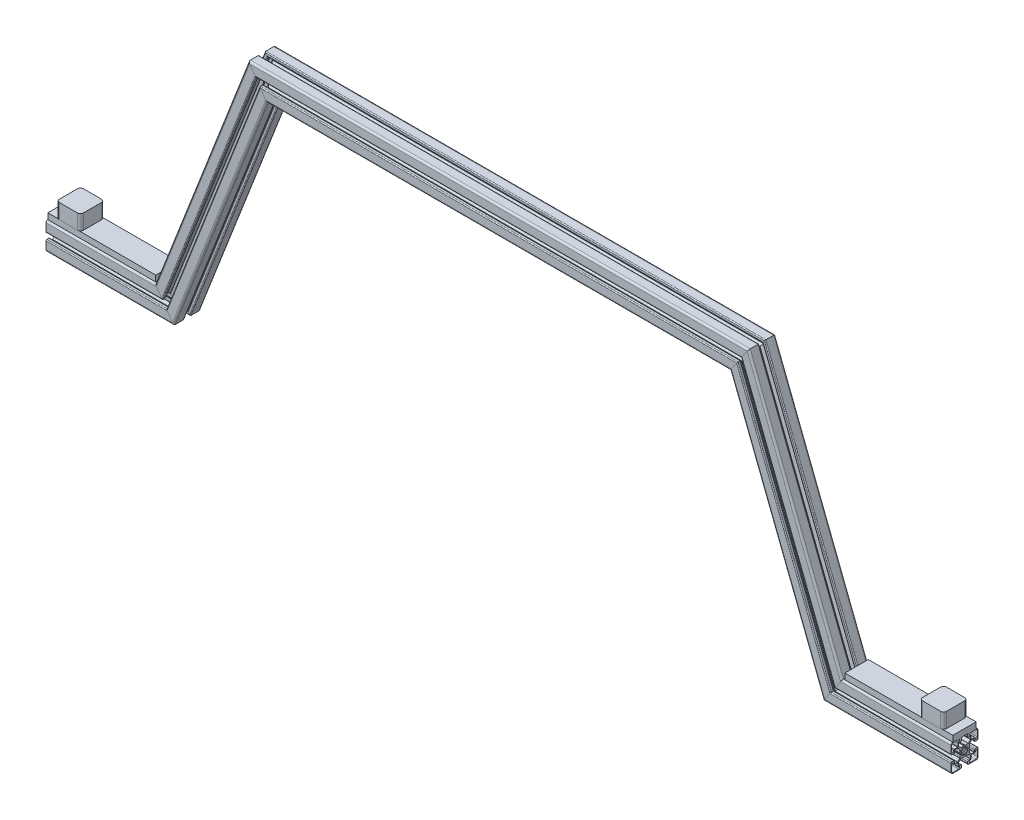
SolidWorks part; units mm, degrees
material "Commercially Pure CP-Ti UNS R50400 (SS)"
ref_plane "Front Plane" through (0, 0, 0) normal (0, 0, 1) x (1, 0, 0)
ref_plane "Top Plane" through (0, 0, 0) normal (0, 1, 0) x (1, 0, 0)
ref_plane "Right Plane" through (0, 0, 0) normal (1, 0, 0) x (0, 0, -1)
sketch "Sketch5" plane through (0, 0, 0) normal (1, 0, 0) x (0, 0, -1)
  line L0 (13.9698, 21.2743) -> (13.5298, 21.2743)
  line L1 (12.0298, 22.7743) -> (12.0298, 23.2743)
  line L2 (13.5298, 24.7743) -> (23.1398, 24.7743)
  line L3 (25.4198, 22.4943) -> (25.4198, 12.8843)
  line L4 (23.9198, 11.3843) -> (23.4198, 11.3843)
  line L5 (21.9198, 12.8843) -> (21.9198, 13.3243)
  line L6 (20.9198, 14.3243) -> (15.3498, 14.3243)
  line L7 (14.9698, 14.7043) -> (14.9698, 20.2743)
  line L8 (21.9589, -6.6897) -> (21.9589, -6.2497)
  line L9 (23.4589, -4.7497) -> (23.9589, -4.7497)
  line L10 (25.4589, -6.2497) -> (25.4589, -15.8597)
  line L11 (23.1789, -18.1397) -> (13.5689, -18.1397)
  line L12 (12.0689, -16.6397) -> (12.0689, -16.1397)
  line L13 (13.5689, -14.6397) -> (14.0089, -14.6397)
  line L14 (15.0089, -13.6397) -> (15.0089, -8.0697)
  line L15 (15.3889, -7.6897) -> (20.9589, -7.6897)
  line L16 (-6.0052, -14.6787) -> (-5.5652, -14.6787)
  line L17 (-4.0652, -16.1787) -> (-4.0652, -16.6787)
  line L18 (-5.5652, -18.1787) -> (-15.1752, -18.1787)
  line L19 (-17.4552, -15.8987) -> (-17.4552, -6.2887)
  line L20 (-15.9552, -4.7887) -> (-15.4552, -4.7887)
  line L21 (-13.9552, -6.2887) -> (-13.9552, -6.7287)
  line L22 (-12.9552, -7.7287) -> (-7.3852, -7.7287)
  line L23 (-7.0052, -8.1087) -> (-7.0052, -13.6787)
  line L24 (1.8289, -2.4886) -> (1.4132, -2.3164)
  line L25 (-1.632, 0.7289) -> (-1.8042, 1.1447)
  line L26 (-1.804, 5.4512) -> (-1.6318, 5.867)
  line L27 (1.4134, 8.9121) -> (1.8292, 9.0843)
  line L28 (6.1358, 9.0842) -> (6.5515, 8.912)
  line L29 (9.5966, 5.8667) -> (9.7688, 5.451)
  line L30 (9.7687, 1.1444) -> (9.5965, 0.7287)
  line L31 (6.5512, -2.3165) -> (6.1355, -2.4887)
  line L32 (-13.9942, 13.2853) -> (-13.9942, 12.8453)
  line L33 (-15.4942, 11.3453) -> (-15.9942, 11.3453)
  line L34 (-17.4942, 12.8453) -> (-17.4942, 22.4553)
  line L35 (-15.2142, 24.7353) -> (-5.6042, 24.7353)
  line L36 (-4.1042, 23.2353) -> (-4.1042, 22.7353)
  line L37 (-5.6042, 21.2353) -> (-6.0442, 21.2353)
  line L38 (-7.0442, 20.2353) -> (-7.0442, 14.6653)
  line L39 (-7.4242, 14.2853) -> (-12.9942, 14.2853)
  line L40 (4.9058, 11.2153) -> (4.0058, 10.7002)
  line L41 (4.0058, 10.7002) -> (3.1058, 11.2153)
  line L42 (3.1058, 11.2153) -> (-2.1975, 11.2153)
  line L43 (-2.4662, 11.3266) -> (-5.9329, 14.7933)
  line L44 (-6.0442, 15.062) -> (-6.0442, 19.3553)
  line L45 (-5.6642, 19.7353) -> (-2.5792, 19.7353)
  line L46 (-1.0592, 21.2553) -> (-1.0592, 24.2153)
  line L47 (-2.5792, 25.7353) -> (-15.4942, 25.7353)
  line L48 (-18.4942, 22.7353) -> (-18.4942, 9.8203)
  line L49 (-16.9742, 8.3003) -> (-14.0142, 8.3003)
  line L50 (-12.4942, 9.8203) -> (-12.4942, 12.9053)
  line L51 (-12.1142, 13.2853) -> (-7.8138, 13.2853)
  line L52 (-7.5451, 13.174) -> (-4.0855, 9.7144)
  line L53 (-3.9742, 9.4457) -> (-3.9742, 4.1353)
  line L54 (-3.9742, 4.1353) -> (-3.4546, 3.2353)
  line L55 (-3.4546, 3.2353) -> (-3.9742, 2.3353)
  line L56 (-3.9742, 2.3353) -> (-3.9742, -2.968)
  line L57 (-4.0855, -3.2367) -> (-7.5522, -6.7034)
  line L58 (-7.8209, -6.8147) -> (-12.1142, -6.8147)
  line L59 (-12.4942, -6.4347) -> (-12.4942, -3.3497)
  line L60 (-14.0142, -1.8297) -> (-16.9742, -1.8297)
  line L61 (-18.4942, -3.3497) -> (-18.4942, -16.2647)
  line L62 (-15.4942, -19.2647) -> (-2.5792, -19.2647)
  line L63 (-1.0592, -17.7447) -> (-1.0592, -14.7847)
  line L64 (-2.5792, -13.2647) -> (-5.6642, -13.2647)
  line L65 (-6.0442, -12.8847) -> (-6.0442, -8.5843)
  line L66 (-5.9329, -8.3156) -> (-2.4733, -4.856)
  line L67 (-2.2046, -4.7447) -> (3.1058, -4.7447)
  line L68 (3.1058, -4.7447) -> (4.0058, -4.2295)
  line L69 (4.0058, -4.2295) -> (4.9058, -4.7447)
  line L70 (4.9058, -4.7447) -> (10.2091, -4.7447)
  line L71 (10.4778, -4.856) -> (13.9445, -8.3227)
  line L72 (14.0558, -8.5914) -> (14.0558, -12.8847)
  line L73 (13.6758, -13.2647) -> (10.5908, -13.2647)
  line L74 (9.0708, -14.7847) -> (9.0708, -17.7447)
  line L75 (10.5908, -19.2647) -> (23.5058, -19.2647)
  line L76 (26.5058, -16.2647) -> (26.5058, -3.3497)
  line L77 (24.9858, -1.8297) -> (22.0258, -1.8297)
  line L78 (20.5058, -3.3497) -> (20.5058, -6.4347)
  line L79 (20.1258, -6.8147) -> (15.8254, -6.8147)
  line L80 (15.5567, -6.7034) -> (12.0971, -3.2438)
  line L81 (11.9858, -2.9751) -> (11.9858, 2.3353)
  line L82 (11.9858, 2.3353) -> (11.4662, 3.2353)
  line L83 (11.4662, 3.2353) -> (11.9858, 4.1353)
  line L84 (11.9858, 4.1353) -> (11.9858, 9.4386)
  line L85 (12.0971, 9.7073) -> (15.5638, 13.174)
  line L86 (15.8325, 13.2853) -> (20.1258, 13.2853)
  line L87 (20.5058, 12.9053) -> (20.5058, 9.8203)
  line L88 (22.0258, 8.3003) -> (24.9858, 8.3003)
  line L89 (26.5058, 9.8203) -> (26.5058, 22.7353)
  line L90 (23.5058, 25.7353) -> (10.5908, 25.7353)
  line L91 (9.0708, 24.2153) -> (9.0708, 21.2553)
  line L92 (10.5908, 19.7353) -> (13.6758, 19.7353)
  line L93 (14.0558, 19.3553) -> (14.0558, 15.0549)
  line L94 (13.9445, 14.7862) -> (10.4849, 11.3266)
  line L95 (10.2162, 11.2153) -> (4.9058, 11.2153)
  arc A0 (14.9698, 20.2743) -> (13.9698, 21.2743) centre (13.9698, 20.2743) ccw
  arc A1 (12.0298, 22.7743) -> (13.5298, 21.2743) centre (13.5298, 22.7743) ccw
  arc A2 (13.5298, 24.7743) -> (12.0298, 23.2743) centre (13.5298, 23.2743) ccw
  arc A3 (25.4198, 22.4943) -> (23.1398, 24.7743) centre (23.1398, 22.4943) ccw
  arc A4 (23.9198, 11.3843) -> (25.4198, 12.8843) centre (23.9198, 12.8843) ccw
  arc A5 (21.9198, 12.8843) -> (23.4198, 11.3843) centre (23.4198, 12.8843) ccw
  arc A6 (21.9198, 13.3243) -> (20.9198, 14.3243) centre (20.9198, 13.3243) ccw
  arc A7 (14.9698, 14.7043) -> (15.3498, 14.3243) centre (15.3498, 14.7043) ccw
  arc A8 (20.9589, -7.6897) -> (21.9589, -6.6897) centre (20.9589, -6.6897) ccw
  arc A9 (23.4589, -4.7497) -> (21.9589, -6.2497) centre (23.4589, -6.2497) ccw
  arc A10 (25.4589, -6.2497) -> (23.9589, -4.7497) centre (23.9589, -6.2497) ccw
  arc A11 (23.1789, -18.1397) -> (25.4589, -15.8597) centre (23.1789, -15.8597) ccw
  arc A12 (12.0689, -16.6397) -> (13.5689, -18.1397) centre (13.5689, -16.6397) ccw
  arc A13 (13.5689, -14.6397) -> (12.0689, -16.1397) centre (13.5689, -16.1397) ccw
  arc A14 (14.0089, -14.6397) -> (15.0089, -13.6397) centre (14.0089, -13.6397) ccw
  arc A15 (15.3889, -7.6897) -> (15.0089, -8.0697) centre (15.3889, -8.0697) ccw
  arc A16 (-7.0052, -13.6787) -> (-6.0052, -14.6787) centre (-6.0052, -13.6787) ccw
  arc A17 (-4.0652, -16.1787) -> (-5.5652, -14.6787) centre (-5.5652, -16.1787) ccw
  arc A18 (-5.5652, -18.1787) -> (-4.0652, -16.6787) centre (-5.5652, -16.6787) ccw
  arc A19 (-17.4552, -15.8987) -> (-15.1752, -18.1787) centre (-15.1752, -15.8987) ccw
  arc A20 (-15.9552, -4.7887) -> (-17.4552, -6.2887) centre (-15.9552, -6.2887) ccw
  arc A21 (-13.9552, -6.2887) -> (-15.4552, -4.7887) centre (-15.4552, -6.2887) ccw
  arc A22 (-13.9552, -6.7287) -> (-12.9552, -7.7287) centre (-12.9552, -6.7287) ccw
  arc A23 (-7.0052, -8.1087) -> (-7.3852, -7.7287) centre (-7.3852, -8.1087) ccw
  arc A24 (1.0363, -0.7421) -> (1.4132, -2.3164) centre (1.7959, -1.3925) ccw
  arc A25 (-0.0577, 0.352) -> (1.0363, -0.7421) centre (3.9823, 3.2978) ccw
  arc A26 (-1.632, 0.7289) -> (-0.0577, 0.352) centre (-0.7081, 1.1116) ccw
  arc A27 (-0.9575, 2.5244) -> (-1.8042, 1.1447) centre (-0.8803, 1.5274) ccw
  arc A28 (-0.9574, 4.0715) -> (-0.9575, 2.5244) centre (3.9823, 3.2978) ccw
  arc A29 (-1.804, 5.4512) -> (-0.9574, 4.0715) centre (-0.8802, 5.0686) ccw
  arc A30 (-0.0575, 6.2439) -> (-1.6318, 5.867) centre (-0.708, 5.4843) ccw
  arc A31 (1.0365, 7.3379) -> (-0.0575, 6.2439) centre (3.9823, 3.2978) ccw
  arc A32 (1.4134, 8.9121) -> (1.0365, 7.3379) centre (1.7961, 7.9882) ccw
  arc A33 (3.2089, 8.2376) -> (1.8292, 9.0843) centre (2.2119, 8.1604) ccw
  arc A34 (4.7561, 8.2376) -> (3.2089, 8.2376) centre (3.9823, 3.2978) ccw
  arc A35 (6.1358, 9.0842) -> (4.7561, 8.2376) centre (5.7531, 8.1603) ccw
  arc A36 (6.9284, 7.3377) -> (6.5515, 8.912) centre (6.1688, 7.9881) ccw
  arc A37 (8.0224, 6.2437) -> (6.9284, 7.3377) centre (3.9823, 3.2978) ccw
  arc A38 (9.5966, 5.8667) -> (8.0224, 6.2437) centre (8.6727, 5.484) ccw
  arc A39 (8.9222, 4.0713) -> (9.7688, 5.451) centre (8.845, 5.0683) ccw
  arc A40 (8.9221, 2.5241) -> (8.9222, 4.0713) centre (3.9823, 3.2978) ccw
  arc A41 (9.7687, 1.1444) -> (8.9221, 2.5241) centre (8.8448, 1.5271) ccw
  arc A42 (8.0222, 0.3518) -> (9.5965, 0.7287) centre (8.6726, 1.1113) ccw
  arc A43 (6.9282, -0.7422) -> (8.0222, 0.3518) centre (3.9823, 3.2978) ccw
  arc A44 (6.5512, -2.3165) -> (6.9282, -0.7422) centre (6.1685, -1.3926) ccw
  arc A45 (4.7558, -1.642) -> (6.1355, -2.4887) centre (5.7528, -1.5648) ccw
  arc A46 (3.2086, -1.642) -> (4.7558, -1.642) centre (3.9823, 3.2978) ccw
  arc A47 (1.8289, -2.4886) -> (3.2086, -1.642) centre (2.2116, -1.5647) ccw
  arc A48 (-12.9942, 14.2853) -> (-13.9942, 13.2853) centre (-12.9942, 13.2853) ccw
  arc A49 (-15.4942, 11.3453) -> (-13.9942, 12.8453) centre (-15.4942, 12.8453) ccw
  arc A50 (-17.4942, 12.8453) -> (-15.9942, 11.3453) centre (-15.9942, 12.8453) ccw
  arc A51 (-15.2142, 24.7353) -> (-17.4942, 22.4553) centre (-15.2142, 22.4553) ccw
  arc A52 (-4.1042, 23.2353) -> (-5.6042, 24.7353) centre (-5.6042, 23.2353) ccw
  arc A53 (-5.6042, 21.2353) -> (-4.1042, 22.7353) centre (-5.6042, 22.7353) ccw
  arc A54 (-6.0442, 21.2353) -> (-7.0442, 20.2353) centre (-6.0442, 20.2353) ccw
  arc A55 (-7.4242, 14.2853) -> (-7.0442, 14.6653) centre (-7.4242, 14.6653) ccw
  arc A56 (-2.4662, 11.3266) -> (-2.1975, 11.2153) centre (-2.1975, 11.5953) ccw
  arc A57 (-6.0442, 15.062) -> (-5.9329, 14.7933) centre (-5.6642, 15.062) ccw
  arc A58 (-5.6642, 19.7353) -> (-6.0442, 19.3553) centre (-5.6642, 19.3553) ccw
  arc A59 (-2.5792, 19.7353) -> (-1.0592, 21.2553) centre (-2.5792, 21.2553) ccw
  arc A60 (-1.0592, 24.2153) -> (-2.5792, 25.7353) centre (-2.5792, 24.2153) ccw
  arc A61 (-15.4942, 25.7353) -> (-18.4942, 22.7353) centre (-15.4942, 22.7353) ccw
  arc A62 (-18.4942, 9.8203) -> (-16.9742, 8.3003) centre (-16.9742, 9.8203) ccw
  arc A63 (-14.0142, 8.3003) -> (-12.4942, 9.8203) centre (-14.0142, 9.8203) ccw
  arc A64 (-12.1142, 13.2853) -> (-12.4942, 12.9053) centre (-12.1142, 12.9053) ccw
  arc A65 (-7.5451, 13.174) -> (-7.8138, 13.2853) centre (-7.8138, 12.9053) ccw
  arc A66 (-3.9742, 9.4457) -> (-4.0855, 9.7144) centre (-4.3542, 9.4457) ccw
  arc A67 (-4.0855, -3.2367) -> (-3.9742, -2.968) centre (-4.3542, -2.968) ccw
  arc A68 (-7.8209, -6.8147) -> (-7.5522, -6.7034) centre (-7.8209, -6.4347) ccw
  arc A69 (-12.4942, -6.4347) -> (-12.1142, -6.8147) centre (-12.1142, -6.4347) ccw
  arc A70 (-12.4942, -3.3497) -> (-14.0142, -1.8297) centre (-14.0142, -3.3497) ccw
  arc A71 (-16.9742, -1.8297) -> (-18.4942, -3.3497) centre (-16.9742, -3.3497) ccw
  arc A72 (-18.4942, -16.2647) -> (-15.4942, -19.2647) centre (-15.4942, -16.2647) ccw
  arc A73 (-2.5792, -19.2647) -> (-1.0592, -17.7447) centre (-2.5792, -17.7447) ccw
  arc A74 (-1.0592, -14.7847) -> (-2.5792, -13.2647) centre (-2.5792, -14.7847) ccw
  arc A75 (-6.0442, -12.8847) -> (-5.6642, -13.2647) centre (-5.6642, -12.8847) ccw
  arc A76 (-5.9329, -8.3156) -> (-6.0442, -8.5843) centre (-5.6642, -8.5843) ccw
  arc A77 (-2.2046, -4.7447) -> (-2.4733, -4.856) centre (-2.2046, -5.1247) ccw
  arc A78 (10.4778, -4.856) -> (10.2091, -4.7447) centre (10.2091, -5.1247) ccw
  arc A79 (14.0558, -8.5914) -> (13.9445, -8.3227) centre (13.6758, -8.5914) ccw
  arc A80 (13.6758, -13.2647) -> (14.0558, -12.8847) centre (13.6758, -12.8847) ccw
  arc A81 (10.5908, -13.2647) -> (9.0708, -14.7847) centre (10.5908, -14.7847) ccw
  arc A82 (9.0708, -17.7447) -> (10.5908, -19.2647) centre (10.5908, -17.7447) ccw
  arc A83 (23.5058, -19.2647) -> (26.5058, -16.2647) centre (23.5058, -16.2647) ccw
  arc A84 (26.5058, -3.3497) -> (24.9858, -1.8297) centre (24.9858, -3.3497) ccw
  arc A85 (22.0258, -1.8297) -> (20.5058, -3.3497) centre (22.0258, -3.3497) ccw
  arc A86 (20.1258, -6.8147) -> (20.5058, -6.4347) centre (20.1258, -6.4347) ccw
  arc A87 (15.5567, -6.7034) -> (15.8254, -6.8147) centre (15.8254, -6.4347) ccw
  arc A88 (11.9858, -2.9751) -> (12.0971, -3.2438) centre (12.3658, -2.9751) ccw
  arc A89 (12.0971, 9.7073) -> (11.9858, 9.4386) centre (12.3658, 9.4386) ccw
  arc A90 (15.8325, 13.2853) -> (15.5638, 13.174) centre (15.8325, 12.9053) ccw
  arc A91 (20.5058, 12.9053) -> (20.1258, 13.2853) centre (20.1258, 12.9053) ccw
  arc A92 (20.5058, 9.8203) -> (22.0258, 8.3003) centre (22.0258, 9.8203) ccw
  arc A93 (24.9858, 8.3003) -> (26.5058, 9.8203) centre (24.9858, 9.8203) ccw
  arc A94 (26.5058, 22.7353) -> (23.5058, 25.7353) centre (23.5058, 22.7353) ccw
  arc A95 (10.5908, 25.7353) -> (9.0708, 24.2153) centre (10.5908, 24.2153) ccw
  arc A96 (9.0708, 21.2553) -> (10.5908, 19.7353) centre (10.5908, 21.2553) ccw
  arc A97 (14.0558, 19.3553) -> (13.6758, 19.7353) centre (13.6758, 19.3553) ccw
  arc A98 (13.9445, 14.7862) -> (14.0558, 15.0549) centre (13.6758, 15.0549) ccw
  arc A99 (10.2162, 11.2153) -> (10.4849, 11.3266) centre (10.2162, 11.5953) ccw
sketch "Sketch1" plane through (0, 0, 0) normal (0, 0, 1) x (1, 0, 0)
  line L0 (0, 0) -> (200, 0)
  line L1 (200, 0) -> (355.8974, 400)
  line L2 (355.8974, 400) -> (755.8974, 400)
  dimension "D1" = 400
  dimension "D2" = 200
  dimension "D3" = 400
sketch "Sketch2" [suppressed] plane through (0, 0, 0) normal (1, 0, 0) x (0, 0, -1)
  line L0 (-33.5, -41) -> (-31.5, -41)
  line L1 (-31.5, -43) -> (-42, -43)
  line L2 (-43, -42) -> (-43, -31.5)
  line L3 (-41, -31.5) -> (-41, -33.5)
  line L4 (-40, -34.5) -> (-34.88, -34.5)
  line L5 (-34.5, -34.88) -> (-34.5, -40)
  line L6 (-16.657, -26.2238) -> (-18.284, -25.188)
  line L7 (-19.8123, -26.7162) -> (-18.7764, -28.3429)
  line L8 (-21.0015, -29.2647) -> (-21.4195, -27.3819)
  line L9 (-23.5808, -27.3818) -> (-23.9986, -29.2645)
  line L10 (-26.2238, -28.343) -> (-25.188, -26.716)
  line L11 (-26.7162, -25.1877) -> (-28.3429, -26.2236)
  line L12 (-29.2647, -23.9985) -> (-27.3819, -23.5805)
  line L13 (-27.3818, -21.4192) -> (-29.2645, -21.0014)
  line L14 (-28.343, -18.7762) -> (-26.716, -19.812)
  line L15 (-25.1877, -18.2838) -> (-26.2236, -16.6571)
  line L16 (-23.9985, -15.7353) -> (-23.5805, -17.6181)
  line L17 (-21.4192, -17.6182) -> (-21.0014, -15.7355)
  line L18 (-18.7762, -16.657) -> (-19.812, -18.284)
  line L19 (-18.2838, -19.8123) -> (-16.6571, -18.7764)
  line L20 (-15.7353, -21.0015) -> (-17.6181, -21.4195)
  line L21 (-17.6182, -23.5808) -> (-15.7355, -23.9986)
  line L22 (41, -33.5) -> (41, -31.5)
  line L23 (43, -31.5) -> (43, -42)
  line L24 (42, -43) -> (31.5, -43)
  line L25 (31.5, -41) -> (33.5, -41)
  line L26 (34.5, -40) -> (34.5, -34.88)
  line L27 (34.88, -34.5) -> (40, -34.5)
  line L28 (26.7162, -19.8123) -> (28.3429, -18.7764)
  line L29 (29.2647, -21.0015) -> (27.3819, -21.4195)
  line L30 (27.3818, -23.5808) -> (29.2645, -23.9986)
  line L31 (28.343, -26.2238) -> (26.716, -25.188)
  line L32 (25.1877, -26.7162) -> (26.2236, -28.3429)
  line L33 (23.9985, -29.2647) -> (23.5805, -27.3819)
  line L34 (21.4192, -27.3818) -> (21.0014, -29.2645)
  line L35 (18.7762, -28.343) -> (19.812, -26.716)
  line L36 (18.2838, -25.1877) -> (16.6571, -26.2236)
  line L37 (15.7353, -23.9985) -> (17.6181, -23.5805)
  line L38 (17.6182, -21.4192) -> (15.7355, -21.0014)
  line L39 (16.657, -18.7762) -> (18.284, -19.812)
  line L40 (19.8123, -18.2838) -> (18.7764, -16.6571)
  line L41 (21.0015, -15.7353) -> (21.4195, -17.6181)
  line L42 (23.5808, -17.6182) -> (23.9986, -15.7355)
  line L43 (26.2238, -16.657) -> (25.188, -18.284)
  line L44 (34.5, 34.88) -> (34.5, 40)
  line L45 (33.5, 41) -> (31.5, 41)
  line L46 (31.5, 43) -> (42, 43)
  line L47 (43, 42) -> (43, 31.5)
  line L48 (41, 31.5) -> (41, 33.5)
  line L49 (40, 34.5) -> (34.88, 34.5)
  line L50 (26.7162, 25.1877) -> (28.3429, 26.2236)
  line L51 (29.2647, 23.9985) -> (27.3819, 23.5805)
  line L52 (27.3818, 21.4192) -> (29.2645, 21.0014)
  line L53 (28.343, 18.7762) -> (26.716, 19.812)
  line L54 (25.1877, 18.2838) -> (26.2236, 16.6571)
  line L55 (23.9985, 15.7353) -> (23.5805, 17.6181)
  line L56 (21.4192, 17.6182) -> (21.0014, 15.7355)
  line L57 (18.7762, 16.657) -> (19.812, 18.284)
  line L58 (18.2838, 19.8123) -> (16.6571, 18.7764)
  line L59 (15.7353, 21.0015) -> (17.6181, 21.4195)
  line L60 (17.6182, 23.5808) -> (15.7355, 23.9986)
  line L61 (16.657, 26.2238) -> (18.284, 25.188)
  line L62 (19.8123, 26.7162) -> (18.7764, 28.3429)
  line L63 (21.0015, 29.2647) -> (21.4195, 27.3819)
  line L64 (23.5808, 27.3818) -> (23.9986, 29.2645)
  line L65 (26.2238, 28.343) -> (25.188, 26.716)
  line L66 (-41, 33.5) -> (-41, 31.5)
  line L67 (-43, 31.5) -> (-43, 42)
  line L68 (-42, 43) -> (-31.5, 43)
  line L69 (-31.5, 41) -> (-33.5, 41)
  line L70 (-34.5, 40) -> (-34.5, 34.88)
  line L71 (-34.88, 34.5) -> (-40, 34.5)
  line L72 (-16.657, 18.7762) -> (-18.284, 19.812)
  line L73 (-19.8123, 18.2838) -> (-18.7764, 16.6571)
  line L74 (-21.0015, 15.7353) -> (-21.4195, 17.6181)
  line L75 (-23.5808, 17.6182) -> (-23.9986, 15.7355)
  line L76 (-26.2238, 16.657) -> (-25.188, 18.284)
  line L77 (-26.7162, 19.8123) -> (-28.3429, 18.7764)
  line L78 (-29.2647, 21.0015) -> (-27.3819, 21.4195)
  line L79 (-27.3818, 23.5808) -> (-29.2645, 23.9986)
  line L80 (-28.343, 26.2238) -> (-26.716, 25.188)
  line L81 (-25.1877, 26.7162) -> (-26.2236, 28.3429)
  line L82 (-23.9985, 29.2647) -> (-23.5805, 27.3819)
  line L83 (-21.4192, 27.3818) -> (-21.0014, 29.2645)
  line L84 (-18.7762, 28.343) -> (-19.812, 26.716)
  line L85 (-18.2838, 25.1877) -> (-16.6571, 26.2236)
  line L86 (-15.7353, 23.9985) -> (-17.6181, 23.5805)
  line L87 (-17.6182, 21.4192) -> (-15.7355, 21.0014)
  line L88 (39, -10.16) -> (33.3774, -10.16)
  line L89 (31.9632, -10.7458) -> (29.8203, -12.8887)
  line L90 (29.5516, -13) -> (23.4, -13)
  line L91 (23.4, -13) -> (22.5, -13.5151)
  line L92 (22.5, -13.5151) -> (21.6, -13)
  line L93 (21.6, -13) -> (15, -13)
  line L94 (13, -15) -> (13, -21.6)
  line L95 (13, -21.6) -> (13.5196, -22.5)
  line L96 (13.5196, -22.5) -> (13, -23.4)
  line L97 (13, -23.4) -> (13, -29.5516)
  line L98 (12.8887, -29.8203) -> (11.3787, -31.3303)
  line L99 (10.5, -33.4516) -> (10.5, -40)
  line L100 (11.5, -41) -> (13.5, -41)
  line L101 (13.5, -43) -> (-13.5, -43)
  line L102 (-13.5, -41) -> (-11.5, -41)
  line L103 (-10.5, -40) -> (-10.5, -33.4516)
  line L104 (-11.3787, -31.3303) -> (-12.8887, -29.8203)
  line L105 (-13, -29.5516) -> (-13, -23.4)
  line L106 (-13, -23.4) -> (-13.5196, -22.5)
  line L107 (-13.5196, -22.5) -> (-13, -21.6)
  line L108 (-13, -21.6) -> (-13, -15)
  line L109 (-15, -13) -> (-21.6, -13)
  line L110 (-21.6, -13) -> (-22.5, -13.5151)
  line L111 (-22.5, -13.5151) -> (-23.4, -13)
  line L112 (-23.4, -13) -> (-29.5516, -13)
  line L113 (-29.8203, -12.8887) -> (-31.9632, -10.7458)
  line L114 (-33.3774, -10.16) -> (-39, -10.16)
  line L115 (-41, -12.16) -> (-41, -13.5)
  line L116 (-43, -13.5) -> (-43, 13.5)
  line L117 (-41, 13.5) -> (-41, 12.16)
  line L118 (-39, 10.16) -> (-33.3774, 10.16)
  line L119 (-31.9632, 10.7458) -> (-29.8203, 12.8887)
  line L120 (-29.5516, 13) -> (-23.4, 13)
  line L121 (-23.4, 13) -> (-22.5, 13.5151)
  line L122 (-22.5, 13.5151) -> (-21.6, 13)
  line L123 (-21.6, 13) -> (-15, 13)
  line L124 (-13, 15) -> (-13, 21.6)
  line L125 (-13, 21.6) -> (-13.5196, 22.5)
  line L126 (-13.5196, 22.5) -> (-13, 23.4)
  line L127 (-13, 23.4) -> (-13, 29.5516)
  line L128 (-12.8887, 29.8203) -> (-11.3787, 31.3303)
  line L129 (-10.5, 33.4516) -> (-10.5, 40)
  line L130 (-11.5, 41) -> (-13.5, 41)
  line L131 (-13.5, 43) -> (13.5, 43)
  line L132 (13.5, 41) -> (11.5, 41)
  line L133 (10.5, 40) -> (10.5, 33.4516)
  line L134 (11.3787, 31.3303) -> (12.8887, 29.8203)
  line L135 (13, 29.5516) -> (13, 23.4)
  line L136 (13, 23.4) -> (13.5196, 22.5)
  line L137 (13.5196, 22.5) -> (13, 21.6)
  line L138 (13, 21.6) -> (13, 15)
  line L139 (15, 13) -> (21.6, 13)
  line L140 (21.6, 13) -> (22.5, 13.5151)
  line L141 (22.5, 13.5151) -> (23.4, 13)
  line L142 (23.4, 13) -> (29.5516, 13)
  line L143 (29.8203, 12.8887) -> (31.9581, 10.7509)
  line L144 (33.3723, 10.1651) -> (39, 10.1651)
  line L145 (41, 12.1651) -> (41, 13.5)
  line L146 (43, 13.5) -> (43, -13.5)
  line L147 (41, -13.5) -> (41, -12.16)
  line L148 (45, -15.915) -> (45, 15.915)
  line L149 (43.48, 17.435) -> (40.52, 17.435)
  line L150 (39, 15.915) -> (39, 13.45)
  line L151 (38, 12.45) -> (34.9984, 12.45)
  line L152 (34.7297, 12.5613) -> (32.1113, 15.1797)
  line L153 (32, 15.4484) -> (32, 21.6)
  line L154 (32, 21.6) -> (31.4804, 22.5)
  line L155 (31.4804, 22.5) -> (32, 23.4)
  line L156 (32, 23.4) -> (32, 29.5516)
  line L157 (32.1113, 29.8203) -> (34.7297, 32.4387)
  line L158 (34.9984, 32.55) -> (38, 32.55)
  line L159 (39, 31.55) -> (39, 29.085)
  line L160 (40.52, 27.565) -> (43.48, 27.565)
  line L161 (45, 29.085) -> (45, 42)
  line L162 (42, 45) -> (29.085, 45)
  line L163 (27.565, 43.48) -> (27.565, 40.52)
  line L164 (29.085, 39) -> (31.55, 39)
  line L165 (32.55, 38) -> (32.55, 34.9984)
  line L166 (32.4387, 34.7297) -> (29.8203, 32.1113)
  line L167 (29.5516, 32) -> (23.4, 32)
  line L168 (23.4, 32) -> (22.5, 31.4849)
  line L169 (22.5, 31.4849) -> (21.6, 32)
  line L170 (21.6, 32) -> (15.4484, 32)
  line L171 (15.1797, 32.1113) -> (12.5613, 34.7297)
  line L172 (12.45, 34.9984) -> (12.45, 38)
  line L173 (13.45, 39) -> (15.915, 39)
  line L174 (17.435, 40.52) -> (17.435, 43.48)
  line L175 (15.915, 45) -> (-15.915, 45)
  line L176 (-17.435, 43.48) -> (-17.435, 40.52)
  line L177 (-15.915, 39) -> (-13.45, 39)
  line L178 (-12.45, 38) -> (-12.45, 34.9984)
  line L179 (-12.5613, 34.7297) -> (-15.1797, 32.1113)
  line L180 (-15.4484, 32) -> (-21.6, 32)
  line L181 (-21.6, 32) -> (-22.5, 31.4849)
  line L182 (-22.5, 31.4849) -> (-23.4, 32)
  line L183 (-23.4, 32) -> (-29.5516, 32)
  line L184 (-29.8203, 32.1113) -> (-32.4387, 34.7297)
  line L185 (-32.55, 34.9984) -> (-32.55, 38)
  line L186 (-31.55, 39) -> (-29.085, 39)
  line L187 (-27.565, 40.52) -> (-27.565, 43.48)
  line L188 (-29.085, 45) -> (-42, 45)
  line L189 (-45, 42) -> (-45, 29.085)
  line L190 (-43.48, 27.565) -> (-40.52, 27.565)
  line L191 (-39, 29.085) -> (-39, 31.55)
  line L192 (-38, 32.55) -> (-34.9984, 32.55)
  line L193 (-34.7297, 32.4387) -> (-32.1113, 29.8203)
  line L194 (-32, 29.5516) -> (-32, 23.4)
  line L195 (-32, 23.4) -> (-31.4804, 22.5)
  line L196 (-31.4804, 22.5) -> (-32, 21.6)
  line L197 (-32, 21.6) -> (-32, 15.4484)
  line L198 (-32.1113, 15.1797) -> (-34.7297, 12.5613)
  line L199 (-34.9984, 12.45) -> (-38, 12.45)
  line L200 (-39, 13.45) -> (-39, 15.915)
  line L201 (-40.52, 17.435) -> (-43.48, 17.435)
  line L202 (-45, 15.915) -> (-45, -15.915)
  line L203 (-43.48, -17.435) -> (-40.52, -17.435)
  line L204 (-39, -15.915) -> (-39, -13.45)
  line L205 (-38, -12.45) -> (-34.9984, -12.45)
  line L206 (-34.7297, -12.5613) -> (-32.1113, -15.1797)
  line L207 (-32, -15.4484) -> (-32, -21.6)
  line L208 (-32, -21.6) -> (-31.4804, -22.5)
  line L209 (-31.4804, -22.5) -> (-32, -23.4)
  line L210 (-32, -23.4) -> (-32, -29.5516)
  line L211 (-32.1113, -29.8203) -> (-34.7297, -32.4387)
  line L212 (-34.9984, -32.55) -> (-38, -32.55)
  line L213 (-39, -31.55) -> (-39, -29.085)
  line L214 (-40.52, -27.565) -> (-43.48, -27.565)
  line L215 (-45, -29.085) -> (-45, -42)
  line L216 (-42, -45) -> (-29.085, -45)
  line L217 (-27.565, -43.48) -> (-27.565, -40.52)
  line L218 (-29.085, -39) -> (-31.55, -39)
  line L219 (-32.55, -38) -> (-32.55, -34.9984)
  line L220 (-32.4387, -34.7297) -> (-29.8203, -32.1113)
  line L221 (-29.5516, -32) -> (-23.4, -32)
  line L222 (-23.4, -32) -> (-22.5, -31.4849)
  line L223 (-22.5, -31.4849) -> (-21.6, -32)
  line L224 (-21.6, -32) -> (-15.4484, -32)
  line L225 (-15.1797, -32.1113) -> (-12.5613, -34.7297)
  line L226 (-12.45, -34.9984) -> (-12.45, -38)
  line L227 (-13.45, -39) -> (-15.915, -39)
  line L228 (-17.435, -40.52) -> (-17.435, -43.48)
  line L229 (-15.915, -45) -> (15.915, -45)
  line L230 (17.435, -43.48) -> (17.435, -40.52)
  line L231 (15.915, -39) -> (13.45, -39)
  line L232 (12.45, -38) -> (12.45, -34.9984)
  line L233 (12.5613, -34.7297) -> (15.1797, -32.1113)
  line L234 (15.4484, -32) -> (21.6, -32)
  line L235 (21.6, -32) -> (22.5, -31.4849)
  line L236 (22.5, -31.4849) -> (23.4, -32)
  line L237 (23.4, -32) -> (29.5516, -32)
  line L238 (29.8203, -32.1113) -> (32.4387, -34.7297)
  line L239 (32.55, -34.9984) -> (32.55, -38)
  line L240 (31.55, -39) -> (29.085, -39)
  line L241 (27.565, -40.52) -> (27.565, -43.48)
  line L242 (29.085, -45) -> (42, -45)
  line L243 (45, -42) -> (45, -29.085)
  line L244 (43.48, -27.565) -> (40.52, -27.565)
  line L245 (39, -29.085) -> (39, -31.55)
  line L246 (38, -32.55) -> (34.9984, -32.55)
  line L247 (34.7297, -32.4387) -> (32.1113, -29.8203)
  line L248 (32, -29.5516) -> (32, -23.4)
  line L249 (32, -23.4) -> (31.4804, -22.5)
  line L250 (31.4804, -22.5) -> (32, -21.6)
  line L251 (32, -21.6) -> (32, -15.4484)
  line L252 (32.1113, -15.1797) -> (34.7297, -12.5613)
  line L253 (34.9984, -12.45) -> (38, -12.45)
  line L254 (39, -13.45) -> (39, -15.915)
  line L255 (40.52, -17.435) -> (43.48, -17.435)
  arc A0 (-34.5, -40) -> (-33.5, -41) centre (-33.5, -40) ccw
  arc A1 (-31.5, -43) -> (-31.5, -41) centre (-31.5, -42) ccw
  arc A2 (-43, -42) -> (-42, -43) centre (-42, -42) ccw
  arc A3 (-41, -31.5) -> (-43, -31.5) centre (-42, -31.5) ccw
  arc A4 (-41, -33.5) -> (-40, -34.5) centre (-40, -33.5) ccw
  arc A5 (-34.5, -34.88) -> (-34.88, -34.5) centre (-34.88, -34.88) ccw
  arc A6 (-15.2086, -25.7917) -> (-15.0167, -25.3284) centre (-22.5, -22.5) ccw
  arc A7 (-16.657, -26.2238) -> (-15.2086, -25.7917) centre (-16.12, -25.3802) ccw
  arc A8 (-19.8123, -26.7162) -> (-18.284, -25.188) centre (-22.5, -22.5) ccw
  arc A9 (-19.2085, -29.7915) -> (-18.7764, -28.3429) centre (-19.6199, -28.8801) ccw
  arc A10 (-19.6717, -29.9834) -> (-19.2085, -29.7915) centre (-22.5, -22.5) ccw
  arc A11 (-21.0015, -29.2647) -> (-19.6717, -29.9834) centre (-20.0253, -29.048) ccw
  arc A12 (-23.5808, -27.3818) -> (-21.4195, -27.3819) centre (-22.5, -22.5) ccw
  arc A13 (-25.3284, -29.9833) -> (-23.9986, -29.2645) centre (-24.9749, -29.0479) ccw
  arc A14 (-25.7917, -29.7914) -> (-25.3284, -29.9833) centre (-22.5, -22.5) ccw
  arc A15 (-26.2238, -28.343) -> (-25.7917, -29.7914) centre (-25.3802, -28.88) ccw
  arc A16 (-26.7162, -25.1877) -> (-25.188, -26.716) centre (-22.5, -22.5) ccw
  arc A17 (-29.7915, -25.7915) -> (-28.3429, -26.2236) centre (-28.8801, -25.3801) ccw
  arc A18 (-29.9834, -25.3283) -> (-29.7915, -25.7915) centre (-22.5, -22.5) ccw
  arc A19 (-29.2647, -23.9985) -> (-29.9834, -25.3283) centre (-29.048, -24.9747) ccw
  arc A20 (-27.3818, -21.4192) -> (-27.3819, -23.5805) centre (-22.5, -22.5) ccw
  arc A21 (-29.9833, -19.6716) -> (-29.2645, -21.0014) centre (-29.0479, -20.0251) ccw
  arc A22 (-29.7914, -19.2083) -> (-29.9833, -19.6716) centre (-22.5, -22.5) ccw
  arc A23 (-28.343, -18.7762) -> (-29.7914, -19.2083) centre (-28.88, -19.6198) ccw
  arc A24 (-25.1877, -18.2838) -> (-26.716, -19.812) centre (-22.5, -22.5) ccw
  arc A25 (-25.7915, -15.2085) -> (-26.2236, -16.6571) centre (-25.3801, -16.1199) ccw
  arc A26 (-25.3283, -15.0166) -> (-25.7915, -15.2085) centre (-22.5, -22.5) ccw
  arc A27 (-23.9985, -15.7353) -> (-25.3283, -15.0166) centre (-24.9747, -15.952) ccw
  arc A28 (-21.4192, -17.6182) -> (-23.5805, -17.6181) centre (-22.5, -22.5) ccw
  arc A29 (-19.6716, -15.0167) -> (-21.0014, -15.7355) centre (-20.0251, -15.9521) ccw
  arc A30 (-19.2083, -15.2086) -> (-19.6716, -15.0167) centre (-22.5, -22.5) ccw
  arc A31 (-18.7762, -16.657) -> (-19.2083, -15.2086) centre (-19.6198, -16.12) ccw
  arc A32 (-18.2838, -19.8123) -> (-19.812, -18.284) centre (-22.5, -22.5) ccw
  arc A33 (-15.2085, -19.2085) -> (-16.6571, -18.7764) centre (-16.1199, -19.6199) ccw
  arc A34 (-15.0166, -19.6717) -> (-15.2085, -19.2085) centre (-22.5, -22.5) ccw
  arc A35 (-15.7353, -21.0015) -> (-15.0166, -19.6717) centre (-15.952, -20.0253) ccw
  arc A36 (-17.6182, -23.5808) -> (-17.6181, -21.4195) centre (-22.5, -22.5) ccw
  arc A37 (-15.0167, -25.3284) -> (-15.7355, -23.9986) centre (-15.9521, -24.9749) ccw
  arc A38 (40, -34.5) -> (41, -33.5) centre (40, -33.5) ccw
  arc A39 (43, -31.5) -> (41, -31.5) centre (42, -31.5) ccw
  arc A40 (42, -43) -> (43, -42) centre (42, -42) ccw
  arc A41 (31.5, -41) -> (31.5, -43) centre (31.5, -42) ccw
  arc A42 (33.5, -41) -> (34.5, -40) centre (33.5, -40) ccw
  arc A43 (34.88, -34.5) -> (34.5, -34.88) centre (34.88, -34.88) ccw
  arc A44 (26.7162, -19.8123) -> (25.188, -18.284) centre (22.5, -22.5) ccw
  arc A45 (29.7915, -19.2085) -> (28.3429, -18.7764) centre (28.8801, -19.6199) ccw
  arc A46 (29.9834, -19.6717) -> (29.7915, -19.2085) centre (22.5, -22.5) ccw
  arc A47 (29.2647, -21.0015) -> (29.9834, -19.6717) centre (29.048, -20.0253) ccw
  arc A48 (27.3818, -23.5808) -> (27.3819, -21.4195) centre (22.5, -22.5) ccw
  arc A49 (29.9833, -25.3284) -> (29.2645, -23.9986) centre (29.0479, -24.9749) ccw
  arc A50 (29.7914, -25.7917) -> (29.9833, -25.3284) centre (22.5, -22.5) ccw
  arc A51 (28.343, -26.2238) -> (29.7914, -25.7917) centre (28.88, -25.3802) ccw
  arc A52 (25.1877, -26.7162) -> (26.716, -25.188) centre (22.5, -22.5) ccw
  arc A53 (25.7915, -29.7915) -> (26.2236, -28.3429) centre (25.3801, -28.8801) ccw
  arc A54 (25.3283, -29.9834) -> (25.7915, -29.7915) centre (22.5, -22.5) ccw
  arc A55 (23.9985, -29.2647) -> (25.3283, -29.9834) centre (24.9747, -29.048) ccw
  arc A56 (21.4192, -27.3818) -> (23.5805, -27.3819) centre (22.5, -22.5) ccw
  arc A57 (19.6716, -29.9833) -> (21.0014, -29.2645) centre (20.0251, -29.0479) ccw
  arc A58 (19.2083, -29.7914) -> (19.6716, -29.9833) centre (22.5, -22.5) ccw
  arc A59 (18.7762, -28.343) -> (19.2083, -29.7914) centre (19.6198, -28.88) ccw
  arc A60 (18.2838, -25.1877) -> (19.812, -26.716) centre (22.5, -22.5) ccw
  arc A61 (15.2085, -25.7915) -> (16.6571, -26.2236) centre (16.1199, -25.3801) ccw
  arc A62 (15.0166, -25.3283) -> (15.2085, -25.7915) centre (22.5, -22.5) ccw
  arc A63 (15.7353, -23.9985) -> (15.0166, -25.3283) centre (15.952, -24.9747) ccw
  arc A64 (17.6182, -21.4192) -> (17.6181, -23.5805) centre (22.5, -22.5) ccw
  arc A65 (15.0167, -19.6716) -> (15.7355, -21.0014) centre (15.9521, -20.0251) ccw
  arc A66 (15.2086, -19.2083) -> (15.0167, -19.6716) centre (22.5, -22.5) ccw
  arc A67 (16.657, -18.7762) -> (15.2086, -19.2083) centre (16.12, -19.6198) ccw
  arc A68 (19.8123, -18.2838) -> (18.284, -19.812) centre (22.5, -22.5) ccw
  arc A69 (19.2085, -15.2085) -> (18.7764, -16.6571) centre (19.6199, -16.1199) ccw
  arc A70 (19.6717, -15.0166) -> (19.2085, -15.2085) centre (22.5, -22.5) ccw
  arc A71 (21.0015, -15.7353) -> (19.6717, -15.0166) centre (20.0253, -15.952) ccw
  arc A72 (23.5808, -17.6182) -> (21.4195, -17.6181) centre (22.5, -22.5) ccw
  arc A73 (25.3284, -15.0167) -> (23.9986, -15.7355) centre (24.9749, -15.9521) ccw
  arc A74 (25.7917, -15.2086) -> (25.3284, -15.0167) centre (22.5, -22.5) ccw
  arc A75 (26.2238, -16.657) -> (25.7917, -15.2086) centre (25.3802, -16.12) ccw
  arc A76 (34.5, 34.88) -> (34.88, 34.5) centre (34.88, 34.88) ccw
  arc A77 (34.5, 40) -> (33.5, 41) centre (33.5, 40) ccw
  arc A78 (31.5, 43) -> (31.5, 41) centre (31.5, 42) ccw
  arc A79 (43, 42) -> (42, 43) centre (42, 42) ccw
  arc A80 (41, 31.5) -> (43, 31.5) centre (42, 31.5) ccw
  arc A81 (41, 33.5) -> (40, 34.5) centre (40, 33.5) ccw
  arc A82 (26.7162, 25.1877) -> (25.188, 26.716) centre (22.5, 22.5) ccw
  arc A83 (29.7915, 25.7915) -> (28.3429, 26.2236) centre (28.8801, 25.3801) ccw
  arc A84 (29.9834, 25.3283) -> (29.7915, 25.7915) centre (22.5, 22.5) ccw
  arc A85 (29.2647, 23.9985) -> (29.9834, 25.3283) centre (29.048, 24.9747) ccw
  arc A86 (27.3818, 21.4192) -> (27.3819, 23.5805) centre (22.5, 22.5) ccw
  arc A87 (29.9833, 19.6716) -> (29.2645, 21.0014) centre (29.0479, 20.0251) ccw
  arc A88 (29.7914, 19.2083) -> (29.9833, 19.6716) centre (22.5, 22.5) ccw
  arc A89 (28.343, 18.7762) -> (29.7914, 19.2083) centre (28.88, 19.6198) ccw
  arc A90 (25.1877, 18.2838) -> (26.716, 19.812) centre (22.5, 22.5) ccw
  arc A91 (25.7915, 15.2085) -> (26.2236, 16.6571) centre (25.3801, 16.1199) ccw
  arc A92 (25.3283, 15.0166) -> (25.7915, 15.2085) centre (22.5, 22.5) ccw
  arc A93 (23.9985, 15.7353) -> (25.3283, 15.0166) centre (24.9747, 15.952) ccw
  arc A94 (21.4192, 17.6182) -> (23.5805, 17.6181) centre (22.5, 22.5) ccw
  arc A95 (19.6716, 15.0167) -> (21.0014, 15.7355) centre (20.0251, 15.9521) ccw
  arc A96 (19.2083, 15.2086) -> (19.6716, 15.0167) centre (22.5, 22.5) ccw
  arc A97 (18.7762, 16.657) -> (19.2083, 15.2086) centre (19.6198, 16.12) ccw
  arc A98 (18.2838, 19.8123) -> (19.812, 18.284) centre (22.5, 22.5) ccw
  arc A99 (15.2085, 19.2085) -> (16.6571, 18.7764) centre (16.1199, 19.6199) ccw
  arc A100 (15.0166, 19.6717) -> (15.2085, 19.2085) centre (22.5, 22.5) ccw
  arc A101 (15.7353, 21.0015) -> (15.0166, 19.6717) centre (15.952, 20.0253) ccw
  arc A102 (17.6182, 23.5808) -> (17.6181, 21.4195) centre (22.5, 22.5) ccw
  arc A103 (15.0167, 25.3284) -> (15.7355, 23.9986) centre (15.9521, 24.9749) ccw
  arc A104 (15.2086, 25.7917) -> (15.0167, 25.3284) centre (22.5, 22.5) ccw
  arc A105 (16.657, 26.2238) -> (15.2086, 25.7917) centre (16.12, 25.3802) ccw
  arc A106 (19.8123, 26.7162) -> (18.284, 25.188) centre (22.5, 22.5) ccw
  arc A107 (19.2085, 29.7915) -> (18.7764, 28.3429) centre (19.6199, 28.8801) ccw
  arc A108 (19.6717, 29.9834) -> (19.2085, 29.7915) centre (22.5, 22.5) ccw
  arc A109 (21.0015, 29.2647) -> (19.6717, 29.9834) centre (20.0253, 29.048) ccw
  arc A110 (23.5808, 27.3818) -> (21.4195, 27.3819) centre (22.5, 22.5) ccw
  arc A111 (25.3284, 29.9833) -> (23.9986, 29.2645) centre (24.9749, 29.0479) ccw
  arc A112 (25.7917, 29.7914) -> (25.3284, 29.9833) centre (22.5, 22.5) ccw
  arc A113 (26.2238, 28.343) -> (25.7917, 29.7914) centre (25.3802, 28.88) ccw
  arc A114 (-40, 34.5) -> (-41, 33.5) centre (-40, 33.5) ccw
  arc A115 (-43, 31.5) -> (-41, 31.5) centre (-42, 31.5) ccw
  arc A116 (-42, 43) -> (-43, 42) centre (-42, 42) ccw
  arc A117 (-31.5, 41) -> (-31.5, 43) centre (-31.5, 42) ccw
  arc A118 (-33.5, 41) -> (-34.5, 40) centre (-33.5, 40) ccw
  arc A119 (-34.88, 34.5) -> (-34.5, 34.88) centre (-34.88, 34.88) ccw
  arc A120 (-15.2086, 19.2083) -> (-15.0167, 19.6716) centre (-22.5, 22.5) ccw
  arc A121 (-16.657, 18.7762) -> (-15.2086, 19.2083) centre (-16.12, 19.6198) ccw
  arc A122 (-19.8123, 18.2838) -> (-18.284, 19.812) centre (-22.5, 22.5) ccw
  arc A123 (-19.2085, 15.2085) -> (-18.7764, 16.6571) centre (-19.6199, 16.1199) ccw
  arc A124 (-19.6717, 15.0166) -> (-19.2085, 15.2085) centre (-22.5, 22.5) ccw
  arc A125 (-21.0015, 15.7353) -> (-19.6717, 15.0166) centre (-20.0253, 15.952) ccw
  arc A126 (-23.5808, 17.6182) -> (-21.4195, 17.6181) centre (-22.5, 22.5) ccw
  arc A127 (-25.3284, 15.0167) -> (-23.9986, 15.7355) centre (-24.9749, 15.9521) ccw
  arc A128 (-25.7917, 15.2086) -> (-25.3284, 15.0167) centre (-22.5, 22.5) ccw
  arc A129 (-26.2238, 16.657) -> (-25.7917, 15.2086) centre (-25.3802, 16.12) ccw
  arc A130 (-26.7162, 19.8123) -> (-25.188, 18.284) centre (-22.5, 22.5) ccw
  arc A131 (-29.7915, 19.2085) -> (-28.3429, 18.7764) centre (-28.8801, 19.6199) ccw
  arc A132 (-29.9834, 19.6717) -> (-29.7915, 19.2085) centre (-22.5, 22.5) ccw
  arc A133 (-29.2647, 21.0015) -> (-29.9834, 19.6717) centre (-29.048, 20.0253) ccw
  arc A134 (-27.3818, 23.5808) -> (-27.3819, 21.4195) centre (-22.5, 22.5) ccw
  arc A135 (-29.9833, 25.3284) -> (-29.2645, 23.9986) centre (-29.0479, 24.9749) ccw
  arc A136 (-29.7914, 25.7917) -> (-29.9833, 25.3284) centre (-22.5, 22.5) ccw
  arc A137 (-28.343, 26.2238) -> (-29.7914, 25.7917) centre (-28.88, 25.3802) ccw
  arc A138 (-25.1877, 26.7162) -> (-26.716, 25.188) centre (-22.5, 22.5) ccw
  arc A139 (-25.7915, 29.7915) -> (-26.2236, 28.3429) centre (-25.3801, 28.8801) ccw
  arc A140 (-25.3283, 29.9834) -> (-25.7915, 29.7915) centre (-22.5, 22.5) ccw
  arc A141 (-23.9985, 29.2647) -> (-25.3283, 29.9834) centre (-24.9747, 29.048) ccw
  arc A142 (-21.4192, 27.3818) -> (-23.5805, 27.3819) centre (-22.5, 22.5) ccw
  arc A143 (-19.6716, 29.9833) -> (-21.0014, 29.2645) centre (-20.0251, 29.0479) ccw
  arc A144 (-19.2083, 29.7914) -> (-19.6716, 29.9833) centre (-22.5, 22.5) ccw
  arc A145 (-18.7762, 28.343) -> (-19.2083, 29.7914) centre (-19.6198, 28.88) ccw
  arc A146 (-18.2838, 25.1877) -> (-19.812, 26.716) centre (-22.5, 22.5) ccw
  arc A147 (-15.2085, 25.7915) -> (-16.6571, 26.2236) centre (-16.1199, 25.3801) ccw
  arc A148 (-15.0166, 25.3283) -> (-15.2085, 25.7915) centre (-22.5, 22.5) ccw
  arc A149 (-15.7353, 23.9985) -> (-15.0166, 25.3283) centre (-15.952, 24.9747) ccw
  arc A150 (-17.6182, 21.4192) -> (-17.6181, 23.5805) centre (-22.5, 22.5) ccw
  arc A151 (-15.0167, 19.6716) -> (-15.7355, 21.0014) centre (-15.9521, 20.0251) ccw
  arc A152 (41, -12.16) -> (39, -10.16) centre (39, -12.16) ccw
  arc A153 (33.3774, -10.16) -> (31.9632, -10.7458) centre (33.3774, -12.16) ccw
  arc A154 (29.5516, -13) -> (29.8203, -12.8887) centre (29.5516, -12.62) ccw
  arc A155 (15, -13) -> (13, -15) centre (15, -15) ccw
  arc A156 (12.8887, -29.8203) -> (13, -29.5516) centre (12.62, -29.5516) ccw
  arc A157 (11.3787, -31.3303) -> (10.5, -33.4516) centre (13.5, -33.4516) ccw
  arc A158 (10.5, -40) -> (11.5, -41) centre (11.5, -40) ccw
  arc A159 (13.5, -43) -> (13.5, -41) centre (13.5, -42) ccw
  arc A160 (-13.5, -41) -> (-13.5, -43) centre (-13.5, -42) ccw
  arc A161 (-11.5, -41) -> (-10.5, -40) centre (-11.5, -40) ccw
  arc A162 (-10.5, -33.4516) -> (-11.3787, -31.3303) centre (-13.5, -33.4516) ccw
  arc A163 (-13, -29.5516) -> (-12.8887, -29.8203) centre (-12.62, -29.5516) ccw
  arc A164 (-13, -15) -> (-15, -13) centre (-15, -15) ccw
  arc A165 (-29.8203, -12.8887) -> (-29.5516, -13) centre (-29.5516, -12.62) ccw
  arc A166 (-31.9632, -10.7458) -> (-33.3774, -10.16) centre (-33.3774, -12.16) ccw
  arc A167 (-39, -10.16) -> (-41, -12.16) centre (-39, -12.16) ccw
  arc A168 (-43, -13.5) -> (-41, -13.5) centre (-42, -13.5) ccw
  arc A169 (-41, 13.5) -> (-43, 13.5) centre (-42, 13.5) ccw
  arc A170 (-41, 12.16) -> (-39, 10.16) centre (-39, 12.16) ccw
  arc A171 (-33.3774, 10.16) -> (-31.9632, 10.7458) centre (-33.3774, 12.16) ccw
  arc A172 (-29.5516, 13) -> (-29.8203, 12.8887) centre (-29.5516, 12.62) ccw
  arc A173 (-15, 13) -> (-13, 15) centre (-15, 15) ccw
  arc A174 (-12.8887, 29.8203) -> (-13, 29.5516) centre (-12.62, 29.5516) ccw
  arc A175 (-11.3787, 31.3303) -> (-10.5, 33.4516) centre (-13.5, 33.4516) ccw
  arc A176 (-10.5, 40) -> (-11.5, 41) centre (-11.5, 40) ccw
  arc A177 (-13.5, 43) -> (-13.5, 41) centre (-13.5, 42) ccw
  arc A178 (13.5, 41) -> (13.5, 43) centre (13.5, 42) ccw
  arc A179 (11.5, 41) -> (10.5, 40) centre (11.5, 40) ccw
  arc A180 (10.5, 33.4516) -> (11.3787, 31.3303) centre (13.5, 33.4516) ccw
  arc A181 (13, 29.5516) -> (12.8887, 29.8203) centre (12.62, 29.5516) ccw
  arc A182 (13, 15) -> (15, 13) centre (15, 15) ccw
  arc A183 (29.8203, 12.8887) -> (29.5516, 13) centre (29.5516, 12.62) ccw
  arc A184 (31.9581, 10.7509) -> (33.3723, 10.1651) centre (33.3723, 12.1651) ccw
  arc A185 (39, 10.1651) -> (41, 12.1651) centre (39, 12.1651) ccw
  arc A186 (43, 13.5) -> (41, 13.5) centre (42, 13.5) ccw
  arc A187 (41, -13.5) -> (43, -13.5) centre (42, -13.5) ccw
  arc A188 (45, 15.915) -> (43.48, 17.435) centre (43.48, 15.915) ccw
  arc A189 (40.52, 17.435) -> (39, 15.915) centre (40.52, 15.915) ccw
  arc A190 (38, 12.45) -> (39, 13.45) centre (38, 13.45) ccw
  arc A191 (34.7297, 12.5613) -> (34.9984, 12.45) centre (34.9984, 12.83) ccw
  arc A192 (32, 15.4484) -> (32.1113, 15.1797) centre (32.38, 15.4484) ccw
  arc A193 (32.1113, 29.8203) -> (32, 29.5516) centre (32.38, 29.5516) ccw
  arc A194 (34.9984, 32.55) -> (34.7297, 32.4387) centre (34.9984, 32.17) ccw
  arc A195 (39, 31.55) -> (38, 32.55) centre (38, 31.55) ccw
  arc A196 (39, 29.085) -> (40.52, 27.565) centre (40.52, 29.085) ccw
  arc A197 (43.48, 27.565) -> (45, 29.085) centre (43.48, 29.085) ccw
  arc A198 (45, 42) -> (42, 45) centre (42, 42) ccw
  arc A199 (29.085, 45) -> (27.565, 43.48) centre (29.085, 43.48) ccw
  arc A200 (27.565, 40.52) -> (29.085, 39) centre (29.085, 40.52) ccw
  arc A201 (32.55, 38) -> (31.55, 39) centre (31.55, 38) ccw
  arc A202 (32.4387, 34.7297) -> (32.55, 34.9984) centre (32.17, 34.9984) ccw
  arc A203 (29.5516, 32) -> (29.8203, 32.1113) centre (29.5516, 32.38) ccw
  arc A204 (15.1797, 32.1113) -> (15.4484, 32) centre (15.4484, 32.38) ccw
  arc A205 (12.45, 34.9984) -> (12.5613, 34.7297) centre (12.83, 34.9984) ccw
  arc A206 (13.45, 39) -> (12.45, 38) centre (13.45, 38) ccw
  arc A207 (15.915, 39) -> (17.435, 40.52) centre (15.915, 40.52) ccw
  arc A208 (17.435, 43.48) -> (15.915, 45) centre (15.915, 43.48) ccw
  arc A209 (-15.915, 45) -> (-17.435, 43.48) centre (-15.915, 43.48) ccw
  arc A210 (-17.435, 40.52) -> (-15.915, 39) centre (-15.915, 40.52) ccw
  arc A211 (-12.45, 38) -> (-13.45, 39) centre (-13.45, 38) ccw
  arc A212 (-12.5613, 34.7297) -> (-12.45, 34.9984) centre (-12.83, 34.9984) ccw
  arc A213 (-15.4484, 32) -> (-15.1797, 32.1113) centre (-15.4484, 32.38) ccw
  arc A214 (-29.8203, 32.1113) -> (-29.5516, 32) centre (-29.5516, 32.38) ccw
  arc A215 (-32.55, 34.9984) -> (-32.4387, 34.7297) centre (-32.17, 34.9984) ccw
  arc A216 (-31.55, 39) -> (-32.55, 38) centre (-31.55, 38) ccw
  arc A217 (-29.085, 39) -> (-27.565, 40.52) centre (-29.085, 40.52) ccw
  arc A218 (-27.565, 43.48) -> (-29.085, 45) centre (-29.085, 43.48) ccw
  arc A219 (-42, 45) -> (-45, 42) centre (-42, 42) ccw
  arc A220 (-45, 29.085) -> (-43.48, 27.565) centre (-43.48, 29.085) ccw
  arc A221 (-40.52, 27.565) -> (-39, 29.085) centre (-40.52, 29.085) ccw
  arc A222 (-38, 32.55) -> (-39, 31.55) centre (-38, 31.55) ccw
  arc A223 (-34.7297, 32.4387) -> (-34.9984, 32.55) centre (-34.9984, 32.17) ccw
  arc A224 (-32, 29.5516) -> (-32.1113, 29.8203) centre (-32.38, 29.5516) ccw
  arc A225 (-32.1113, 15.1797) -> (-32, 15.4484) centre (-32.38, 15.4484) ccw
  arc A226 (-34.9984, 12.45) -> (-34.7297, 12.5613) centre (-34.9984, 12.83) ccw
  arc A227 (-39, 13.45) -> (-38, 12.45) centre (-38, 13.45) ccw
  arc A228 (-39, 15.915) -> (-40.52, 17.435) centre (-40.52, 15.915) ccw
  arc A229 (-43.48, 17.435) -> (-45, 15.915) centre (-43.48, 15.915) ccw
  arc A230 (-45, -15.915) -> (-43.48, -17.435) centre (-43.48, -15.915) ccw
  arc A231 (-40.52, -17.435) -> (-39, -15.915) centre (-40.52, -15.915) ccw
  arc A232 (-38, -12.45) -> (-39, -13.45) centre (-38, -13.45) ccw
  arc A233 (-34.7297, -12.5613) -> (-34.9984, -12.45) centre (-34.9984, -12.83) ccw
  arc A234 (-32, -15.4484) -> (-32.1113, -15.1797) centre (-32.38, -15.4484) ccw
  arc A235 (-32.1113, -29.8203) -> (-32, -29.5516) centre (-32.38, -29.5516) ccw
  arc A236 (-34.9984, -32.55) -> (-34.7297, -32.4387) centre (-34.9984, -32.17) ccw
  arc A237 (-39, -31.55) -> (-38, -32.55) centre (-38, -31.55) ccw
  arc A238 (-39, -29.085) -> (-40.52, -27.565) centre (-40.52, -29.085) ccw
  arc A239 (-43.48, -27.565) -> (-45, -29.085) centre (-43.48, -29.085) ccw
  arc A240 (-45, -42) -> (-42, -45) centre (-42, -42) ccw
  arc A241 (-29.085, -45) -> (-27.565, -43.48) centre (-29.085, -43.48) ccw
  arc A242 (-27.565, -40.52) -> (-29.085, -39) centre (-29.085, -40.52) ccw
  arc A243 (-32.55, -38) -> (-31.55, -39) centre (-31.55, -38) ccw
  arc A244 (-32.4387, -34.7297) -> (-32.55, -34.9984) centre (-32.17, -34.9984) ccw
  arc A245 (-29.5516, -32) -> (-29.8203, -32.1113) centre (-29.5516, -32.38) ccw
  arc A246 (-15.1797, -32.1113) -> (-15.4484, -32) centre (-15.4484, -32.38) ccw
  arc A247 (-12.45, -34.9984) -> (-12.5613, -34.7297) centre (-12.83, -34.9984) ccw
  arc A248 (-13.45, -39) -> (-12.45, -38) centre (-13.45, -38) ccw
  arc A249 (-15.915, -39) -> (-17.435, -40.52) centre (-15.915, -40.52) ccw
  arc A250 (-17.435, -43.48) -> (-15.915, -45) centre (-15.915, -43.48) ccw
  arc A251 (15.915, -45) -> (17.435, -43.48) centre (15.915, -43.48) ccw
  arc A252 (17.435, -40.52) -> (15.915, -39) centre (15.915, -40.52) ccw
  arc A253 (12.45, -38) -> (13.45, -39) centre (13.45, -38) ccw
  arc A254 (12.5613, -34.7297) -> (12.45, -34.9984) centre (12.83, -34.9984) ccw
  arc A255 (15.4484, -32) -> (15.1797, -32.1113) centre (15.4484, -32.38) ccw
  arc A256 (29.8203, -32.1113) -> (29.5516, -32) centre (29.5516, -32.38) ccw
  arc A257 (32.55, -34.9984) -> (32.4387, -34.7297) centre (32.17, -34.9984) ccw
  arc A258 (31.55, -39) -> (32.55, -38) centre (31.55, -38) ccw
  arc A259 (29.085, -39) -> (27.565, -40.52) centre (29.085, -40.52) ccw
  arc A260 (27.565, -43.48) -> (29.085, -45) centre (29.085, -43.48) ccw
  arc A261 (42, -45) -> (45, -42) centre (42, -42) ccw
  arc A262 (45, -29.085) -> (43.48, -27.565) centre (43.48, -29.085) ccw
  arc A263 (40.52, -27.565) -> (39, -29.085) centre (40.52, -29.085) ccw
  arc A264 (38, -32.55) -> (39, -31.55) centre (38, -31.55) ccw
  arc A265 (34.7297, -32.4387) -> (34.9984, -32.55) centre (34.9984, -32.17) ccw
  arc A266 (32, -29.5516) -> (32.1113, -29.8203) centre (32.38, -29.5516) ccw
  arc A267 (32.1113, -15.1797) -> (32, -15.4484) centre (32.38, -15.4484) ccw
  arc A268 (34.9984, -12.45) -> (34.7297, -12.5613) centre (34.9984, -12.83) ccw
  arc A269 (39, -13.45) -> (38, -12.45) centre (38, -13.45) ccw
  arc A270 (39, -15.915) -> (40.52, -17.435) centre (40.52, -15.915) ccw
  arc A271 (43.48, -17.435) -> (45, -15.915) centre (43.48, -15.915) ccw
sweep "Sweep1" add profiles "Sketch5" path "Sketch1"
ref_plane "Plane1" through (755.8974, 0, 0) normal (1, 0, 0) x (0, 0, -1)
sketch "Sketch3" plane through (0, 25.7353, 0) normal (0, 1, 0) x (1, 0, 0)
  line L0 (0, 23.5058) -> (182.4093, 23.5058) construction
  line L1 (0, 23.5058) -> (180.2874, 23.5058)
  line L2 (0, 23.5058) -> (0, -15.4942)
  line L3 (0, -15.4942) -> (180.2874, -15.4942)
  line L4 (180.2874, 23.5058) -> (180.2874, -15.4942)
  line L5 (0, -15.4942) -> (182.4093, -15.4942) construction
  point P6 (0, 42)
  point P7 (0, 23.5058)
  point P10 (0, -42)
  point P11 (0, -42)
  point P12 (0, -42)
  point P13 (180.2874, -15.4942)
extrude "Boss-Extrude1" add sketch "Sketch3" along normal blind 10
sketch "Sketch4" plane through (0, 35.7353, 0) normal (0, 1, 0) x (1, 0, 0)
  line L0 (0, 4.0058) -> (180.2874, 4.0058) construction
  line L3 (0, 23.5058) -> (0, -15.4942) construction
  line L8 (180.2874, -15.4942) -> (180.2874, 23.5058) construction
  line L10 (15, -15.9942) -> (55, -15.9942)
  line L11 (15, -15.9942) -> (15, 24.0058)
  line L12 (15, 24.0058) -> (55, 24.0058)
  line L13 (55, -15.9942) -> (55, 24.0058)
  line L14 (15, -15.9942) -> (55, 24.0058) construction
  line L15 (15, 24.0058) -> (55, -15.9942) construction
  point P6 (84.6207, -22)
  point P7 (35, 4.0058)
  dimension "D1" = 40
  dimension "D2" = 40
  dimension "D3" = 15
extrude "Boss-Extrude2" add sketch "Sketch4" along normal blind 25
fillet "Fillet1" radius 5 4 edges at (55, 48.2353, -24.0058) (55, 48.2353, 15.9942) (15, 48.2353, -24.0058) (15, 48.2353, 15.9942)
mirror "Mirror1" about plane through (755.8974, 0, 0) normal (1, 0, 0) of "Boss-Extrude2", "Fillet1", "Boss-Extrude1", "Sweep1"
